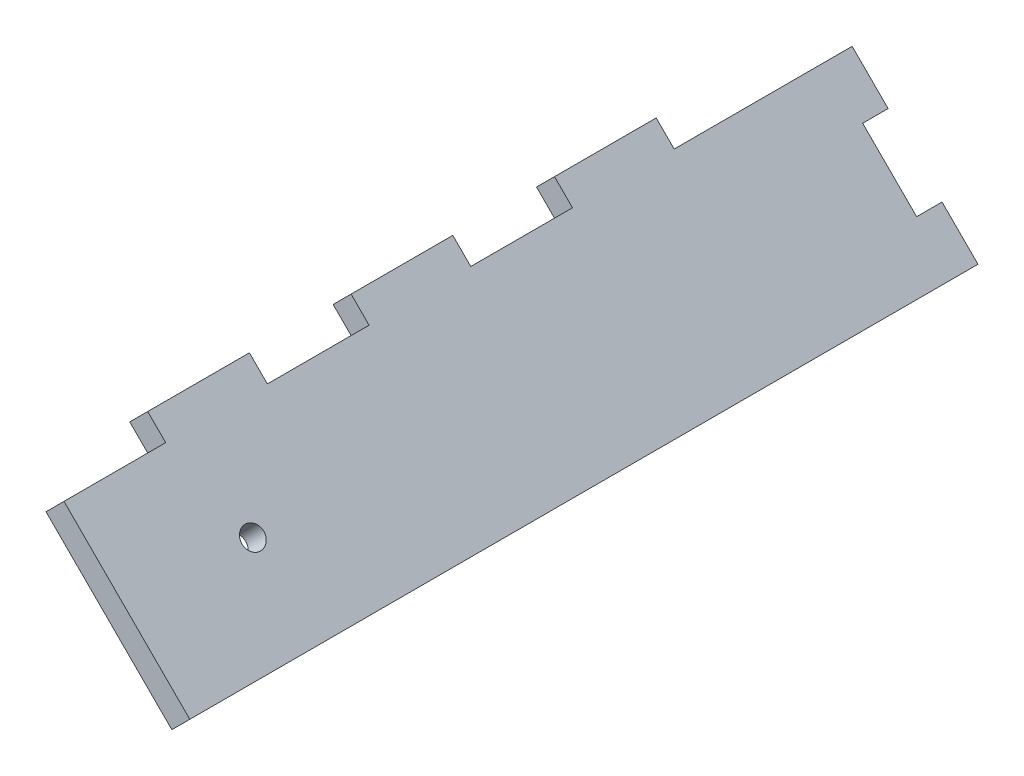
SolidWorks part; units mm, degrees
ref_plane "Front Plane" through (0, 0, 0) normal (0, 0, 1) x (1, 0, 0)
ref_plane "Top Plane" through (0, 0, 0) normal (0, 1, 0) x (1, 0, 0)
ref_plane "Right Plane" through (0, 0, 0) normal (1, 0, 0) x (0, 0, -1)
sketch "Sketch1" plane through (0, 0, 0) normal (0, 0, 1) x (1, 0, 0)
  line L0 (-105.5101, 43.1479) -> (-54.0999, -8.2622) construction
  line L1 (29.2392, -96.0914) -> (-8.57, -58.2823) construction
  line L2 (-4.0799, -53.7921) -> (33.7293, -91.6013) construction
  line L3 (-71.393, 41.3598) -> (-39.9621, 9.9289)
  line L4 (-71.393, 41.3598) -> (-66.9029, 45.85)
  line L5 (-39.9621, 9.9289) -> (-35.472, 14.4191)
  line L6 (-66.9029, 45.85) -> (-35.472, 14.4191)
  line L7 (-72.2911, -22.4) -> (-103.722, 9.0309) construction
  line L8 (-76.7812, -26.8901) -> (-72.2911, -22.4) construction
extrude "Boss-Extrude1" add sketch "Sketch1" along normal up to surface (190.5 mm away)
sketch "Sketch2" plane through (-56.3764, 56.3764, 0) normal (-0.7071, 0.7071, 0) x (0, 0, 1)
  line L0 (190.5, -14.8867) -> (0, -14.8867) construction
  line L1 (165.1, -14.8867) -> (139.7, -14.8867)
  line L2 (165.1, -14.8867) -> (165.1, -21.2367)
  line L3 (165.1, -21.2367) -> (139.7, -21.2367)
  line L4 (139.7, -14.8867) -> (139.7, -21.2367)
  line L5 (190.5, -21.2367) -> (0, -21.2367) construction
  dimension "D1" = 25.4
  dimension "D2" = 25.4
extrude "Boss-Extrude2" add sketch "Sketch2" along normal blind 6.35
pattern_linear "LPattern1" count 3 spacing 50.8 along (0, 0, -1) of "Boss-Extrude2"
sketch "Sketch3" plane through (0, 0, 0) normal (0, 0, -1) x (-1, 0, 0)
  line L0 (71.393, 41.3598) -> (62.4128, 32.3796)
  line L1 (71.393, 41.3598) -> (39.9621, 9.9289) construction
  line L2 (62.4128, 32.3796) -> (57.9227, 36.8697)
  line L3 (35.472, 14.4191) -> (66.9029, 45.85) construction
  line L4 (57.9227, 36.8697) -> (66.9029, 45.85)
  line L5 (66.9029, 45.85) -> (71.393, 41.3598)
  dimension "D1" = 12.7
extrude "Boss-Extrude3" add sketch "Sketch3" along normal blind 6.35
pattern_linear "LPattern2" count 2 spacing 31.75 along (0.7071, -0.7071, 0) of "Boss-Extrude3"
sketch "Sketch4" plane through (-10.5265, -10.5265, 0) normal (0.7071, 0.7071, 0) x (0, 0, -1)
  circle A0 centre (-159.0375, 57.5033) radius 2.7305
extrude "Cut-Extrude1" cut sketch "Sketch4" against normal through all
